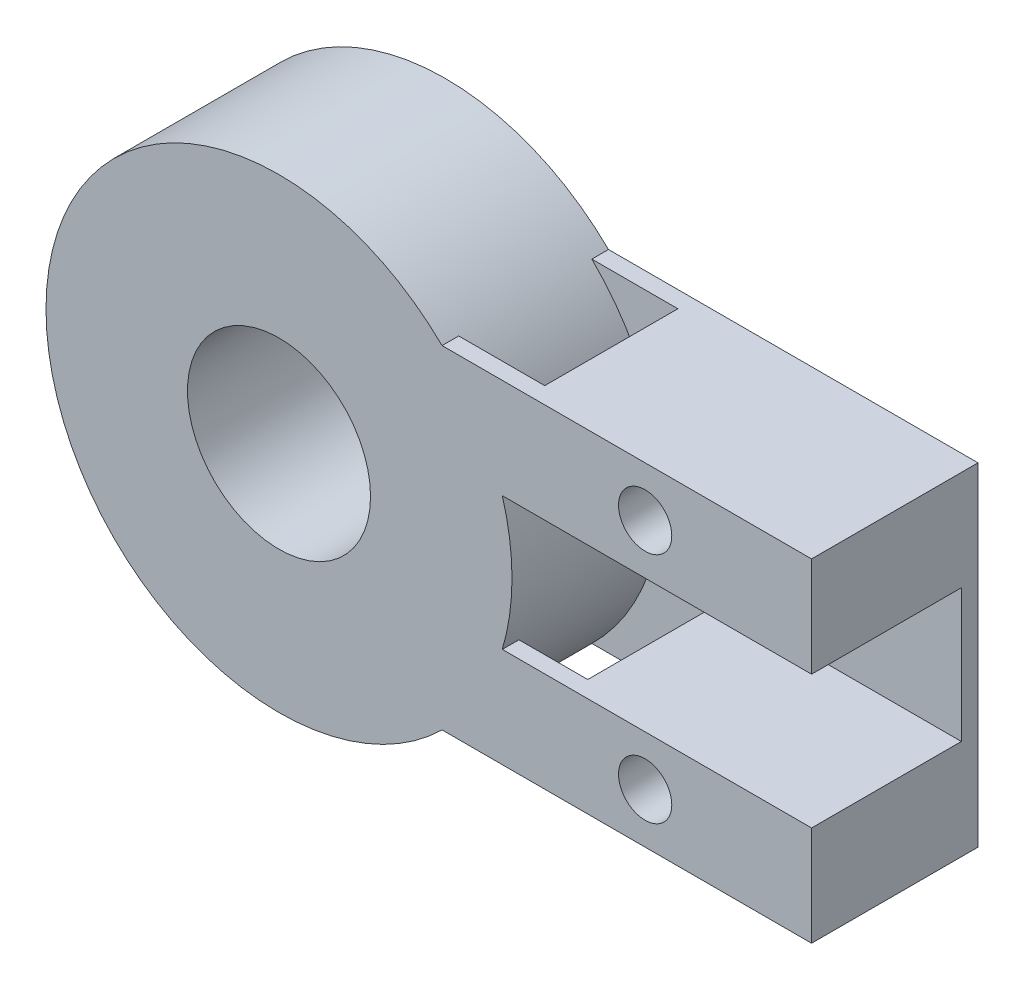
SolidWorks part; units mm, degrees
ref_plane "Front Plane" through (0, 0, 0) normal (0, 0, 1) x (1, 0, 0)
ref_plane "Top Plane" through (0, 0, 0) normal (0, 1, 0) x (1, 0, 0)
ref_plane "Right Plane" through (0, 0, 0) normal (1, 0, 0) x (0, 0, -1)
sketch "Sketch1" plane through (0, 0, 0) normal (0, 0, 1) x (1, 0, 0)
  line L0 (6.4561, 14.1537) -> (6.4561, 19.1537) construction
  line L1 (6.4561, 14.1537) -> (6.4561, 9.1537) construction
  line L2 (13.4561, 14.1537) -> (22.4561, 14.1537) construction
  line L3 (22.4561, 19.1537) -> (11.3551, 19.1537)
  line L4 (22.4561, 14.1537) -> (22.4561, 19.1537)
  line L5 (22.4561, 9.1537) -> (11.3551, 9.1537)
  line L6 (22.4561, 14.1537) -> (22.4561, 9.1537)
  line L7 (6.4561, 14.1537) -> (32.4561, 14.1537) construction
  circle A0 centre (6.4561, 14.1537) radius 7
sketch "Sketch2" plane through (0, 0, 0) normal (0, 0, 1) x (1, 0, 0)
  line L0 (6.4561, 14.1537) -> (-0.5439, 14.1537) construction
  line L1 (6.4561, 14.1537) -> (15.9561, 14.1537) construction
  line L2 (6.4561, 14.1537) -> (6.4561, 19.6537) construction
  line L3 (6.4561, 14.1537) -> (6.4561, 8.6537) construction
  line L4 (-0.5439, 14.1537) -> (-0.5439, 12.6537)
  line L5 (-0.5439, 12.6537) -> (0.9561, 12.6537)
  line L6 (0.9561, 12.6537) -> (2.4561, 12.6537) construction
  line L7 (2.4561, 12.6537) -> (2.4561, 9.6537) construction
  line L8 (0.9561, 12.6537) -> (2.4561, 9.6537)
  line L9 (2.4561, 9.6537) -> (2.4561, 8.6537)
  line L10 (2.4561, 8.6537) -> (6.4561, 8.6537)
  line L11 (6.4561, 8.6537) -> (10.7061, 8.6537)
  line L12 (10.7061, 8.6537) -> (10.7061, 9.6537)
  line L13 (10.7061, 9.6537) -> (15.9561, 9.6537)
  line L14 (15.9561, 9.6537) -> (15.9561, 14.1537)
  line L15 (-0.5439, 14.1537) -> (-0.5439, 15.6537)
  line L16 (-0.5439, 15.6537) -> (0.9561, 15.6537)
  line L17 (0.9561, 15.6537) -> (2.4561, 15.6537) construction
  line L18 (2.4561, 15.6537) -> (2.4561, 18.6537) construction
  line L19 (0.9561, 15.6537) -> (2.4561, 18.6537)
  line L20 (2.4561, 18.6537) -> (2.4561, 19.6537)
  line L21 (2.4561, 19.6537) -> (6.4561, 19.6537)
  line L22 (6.4561, 19.6537) -> (10.7061, 19.6537)
  line L23 (10.7061, 19.6537) -> (10.7061, 18.6537)
  line L24 (10.7061, 18.6537) -> (15.9561, 18.6537)
  line L25 (15.9561, 18.6537) -> (15.9561, 14.1537)
extrude "Boss-Extrude1" add sketch "Sketch1" along normal blind 5 contours A0 | A0 region at (17.6109, 14.1537, 0) region at (6.4561, 14.1537, 0)
sketch "Sketch3" plane through (0, 0, 0) normal (0, 0, 1) x (1, 0, 0)
  circle A0 centre (6.4561, 14.1537) radius 2.75
extrude "Joint Hole" cut sketch "Sketch3" along normal through all
sketch "Sketch8" plane through (0, 0, 0) normal (0, 0, 1) x (1, 0, 0)
  line L0 (22.4561, 14.1537) -> (22.4561, 16.1537)
  line L2 (22.4561, 14.1537) -> (15.4561, 14.1537) construction
  line L3 (22.4561, 19.1537) -> (22.4561, 9.1537) construction
  line L4 (22.4561, 16.1537) -> (15.231, 16.1537)
  line L5 (22.4561, 14.1537) -> (22.4561, 12.1537)
  line L6 (11.3551, 19.1537) -> (13.9394, 19.1537)
  line L7 (22.4561, 19.1537) -> (11.3551, 19.1537) construction
  line L8 (11.3551, 9.1537) -> (13.9394, 9.1537)
  line L9 (22.4561, 12.1537) -> (15.231, 12.1537)
  circle A0 centre (6.4561, 14.1537) radius 7
  circle A1 centre (6.4561, 14.1537) radius 9
extrude "Cut-Extrude2" cut sketch "Sketch8" along normal blind 5.5 from offset 0.5 contours A1 | A1 L6 A0 L8 | L5 L2 A1 L9 region at (18.9185, 15.159, 0) region at (18.9185, 13.1484, 0) region at (13.8468, 14.1537, 0)
sketch "Sketch7" plane through (0, 0, 0) normal (0, 0, 1) x (1, 0, 0)
  line L1 (6.4561, 14.1537) -> (17.4561, 14.1537) construction
  line L4 (17.4561, 14.1537) -> (17.4561, 17.6537) construction
  line L6 (17.4561, 14.1537) -> (17.4561, 10.6537) construction
  circle A0 centre (17.4561, 17.6537) radius 0.8
  circle A1 centre (17.4561, 10.6537) radius 0.8
extrude "Screw Holes" cut sketch "Sketch7" along normal through all
sketch "Sketch10" plane through (0, 0, 0) normal (0, 0, 1) x (1, 0, 0)
  line L1 (11.3551, 19.1537) -> (15.231, 19.1537)
  line L2 (11.3551, 19.1537) -> (11.3551, 16.1537)
  line L3 (11.3551, 16.1537) -> (15.231, 16.1537)
  line L4 (15.231, 19.1537) -> (15.231, 16.1537)
  line L5 (11.3551, 9.1537) -> (15.231, 9.1537)
  line L6 (11.3551, 9.1537) -> (11.3551, 12.1537)
  line L7 (11.3551, 12.1537) -> (15.231, 12.1537)
  line L8 (15.231, 9.1537) -> (15.231, 12.1537)
extrude "Boss-Extrude2" add sketch "Sketch10" against normal blind 0.5 from offset 5
